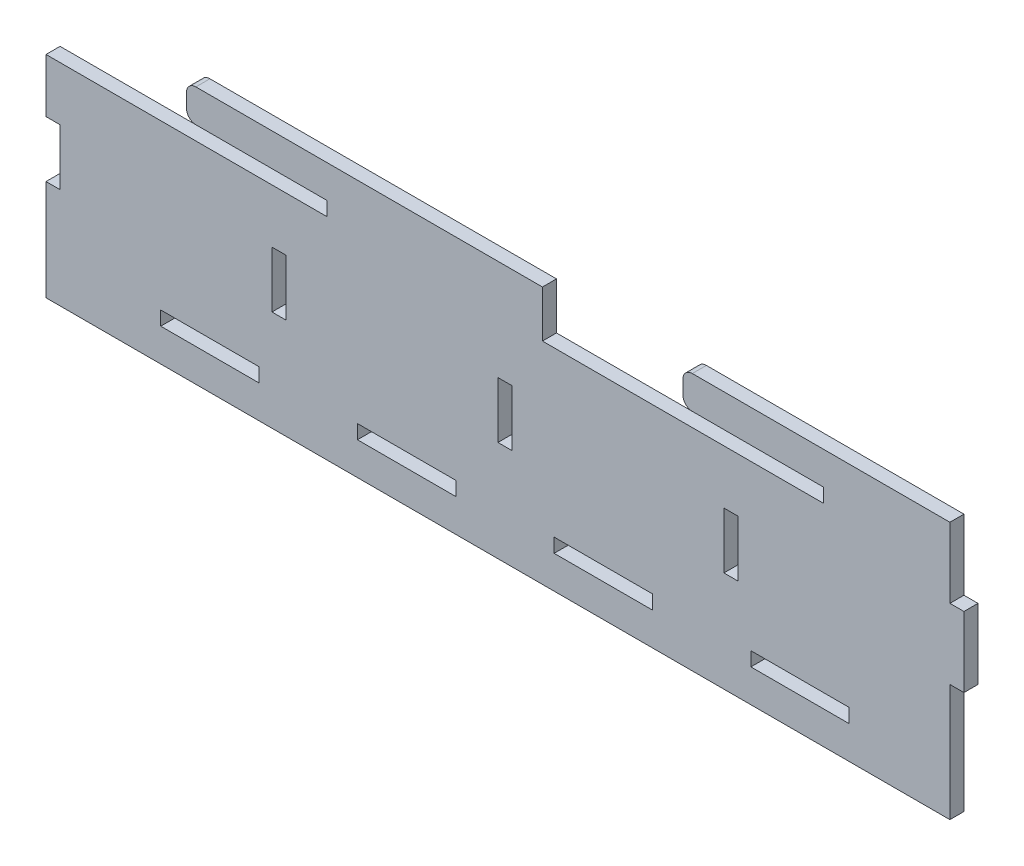
SolidWorks part; units mm, degrees
ref_plane "Front Plane" through (0, 0, 0) normal (0, 0, 1) x (1, 0, 0)
ref_plane "Top Plane" through (0, 0, 0) normal (0, 1, 0) x (1, 0, 0)
ref_plane "Right Plane" through (0, 0, 0) normal (1, 0, 0) x (0, 0, -1)
sketch "Sketch1" plane through (0, 0, 0) normal (0, 0, 1) x (1, 0, 0)
  line L0 (-102.4545, -7.25) -> (-99.4545, -7.25)
  line L1 (-102.4545, -28.75) -> (93.5455, -28.75)
  line L2 (-102.4545, -28.75) -> (-102.4545, 26.25)
  line L3 (-102.4545, 26.25) -> (93.5455, 26.25)
  line L4 (93.5455, -28.75) -> (93.5455, 26.25)
  line L5 (-102.4545, -28.75) -> (93.5455, 26.25) construction
  line L6 (-102.4545, 26.25) -> (93.5455, -28.75) construction
  line L7 (-99.4545, -7.25) -> (-99.4545, 4.75)
  line L8 (-99.4545, 4.75) -> (-102.4545, 4.75)
  line L9 (90.5455, -28.75) -> (90.5455, -3.75)
  line L10 (90.5455, -3.75) -> (93.5455, -3.75)
  line L11 (90.5455, 26.25) -> (90.5455, 11.25)
  line L12 (90.5455, 11.25) -> (93.5455, 11.25)
  line L13 (-72.4545, 26.25) -> (-72.4545, 19.25)
  line L14 (-54.2045, -7.25) -> (-51.2045, -7.25)
  line L15 (-54.2045, -7.25) -> (-54.2045, 4.75)
  line L16 (-54.2045, 4.75) -> (-51.2045, 4.75)
  line L17 (-51.2045, -7.25) -> (-51.2045, 4.75)
  line L18 (-54.2045, -7.25) -> (-51.2045, 4.75) construction
  line L19 (-54.2045, 4.75) -> (-51.2045, -7.25) construction
  line L20 (-5.9545, -7.25) -> (-2.9545, -7.25)
  line L21 (-5.9545, -7.25) -> (-5.9545, 4.75)
  line L22 (-5.9545, 4.75) -> (-2.9545, 4.75)
  line L23 (-2.9545, -7.25) -> (-2.9545, 4.75)
  line L24 (-5.9545, -7.25) -> (-2.9545, 4.75) construction
  line L25 (-5.9545, 4.75) -> (-2.9545, -7.25) construction
  line L26 (45.2955, -7.25) -> (42.2955, -7.25)
  line L27 (45.2955, -7.25) -> (45.2955, 4.75)
  line L28 (45.2955, 4.75) -> (42.2955, 4.75)
  line L29 (42.2955, -7.25) -> (42.2955, 4.75)
  line L30 (45.2955, -7.25) -> (42.2955, 4.75) construction
  line L31 (45.2955, 4.75) -> (42.2955, -7.25) construction
  line L32 (-72.4545, 19.25) -> (-42.4545, 19.25)
  line L33 (-42.4545, 19.25) -> (-42.4545, 16.25)
  line L34 (-42.4545, 16.25) -> (-102.4545, 16.25)
  line L35 (3.5455, 26.25) -> (3.5455, 16.25)
  line L36 (3.5455, 16.25) -> (63.5455, 16.25)
  line L37 (63.5455, 16.25) -> (63.5455, 19.25)
  line L38 (63.5455, 19.25) -> (33.5455, 19.25)
  line L39 (33.5455, 19.25) -> (33.5455, 26.25)
  line L41 (-77.9545, -21.75) -> (-56.9545, -21.75)
  line L42 (-77.9545, -21.75) -> (-77.9545, -18.75)
  line L43 (-77.9545, -18.75) -> (-56.9545, -18.75)
  line L44 (-56.9545, -21.75) -> (-56.9545, -18.75)
  line L45 (-77.9545, -21.75) -> (-56.9545, -18.75) construction
  line L46 (-77.9545, -18.75) -> (-56.9545, -21.75) construction
  line L47 (27.0455, -21.75) -> (6.0455, -21.75)
  line L48 (27.0455, -21.75) -> (27.0455, -18.75)
  line L49 (27.0455, -18.75) -> (6.0455, -18.75)
  line L50 (6.0455, -21.75) -> (6.0455, -18.75)
  line L51 (27.0455, -21.75) -> (6.0455, -18.75) construction
  line L52 (27.0455, -18.75) -> (6.0455, -21.75) construction
  line L53 (-14.9545, -21.75) -> (-35.9545, -21.75)
  line L54 (-14.9545, -21.75) -> (-14.9545, -18.75)
  line L55 (-14.9545, -18.75) -> (-35.9545, -18.75)
  line L56 (-35.9545, -21.75) -> (-35.9545, -18.75)
  line L57 (-14.9545, -21.75) -> (-35.9545, -18.75) construction
  line L58 (-14.9545, -18.75) -> (-35.9545, -21.75) construction
  line L71 (48.0455, -21.75) -> (69.0455, -21.75)
  line L72 (48.0455, -21.75) -> (48.0455, -18.75)
  line L73 (48.0455, -18.75) -> (69.0455, -18.75)
  line L74 (69.0455, -21.75) -> (69.0455, -18.75)
  line L75 (48.0455, -21.75) -> (69.0455, -18.75) construction
  line L76 (48.0455, -18.75) -> (69.0455, -21.75) construction
  point P0 (-67.4545, -20.25)
  point P43 (16.5455, -20.25)
  point P48 (-25.4545, -20.25)
  point P63 (58.5455, -20.25)
  dimension "D1" = 196
  dimension "D2" = 55
  dimension "D3" = 12
  dimension "D4" = 21.5
  dimension "D5" = 3
  dimension "D6" = 3
  dimension "D7" = 25
  dimension "D8" = 15
  dimension "D9" = 12
  dimension "D10" = 3
  dimension "D11" = 24.5
  dimension "D12" = 45.25
  dimension "D13" = 12
  dimension "D14" = 3
  dimension "D15" = 45.25
  dimension "D16" = 3
  dimension "D17" = 12
  dimension "D18" = 45.25
  dimension "D19" = 21
  dimension "D20" = 30
  dimension "D21" = 30
  dimension "D22" = 3
  dimension "D23" = 7
  dimension "D24" = 30
  dimension "D25" = 30
  dimension "D26" = 30
  dimension "D27" = 3
  dimension "D28" = 7
  dimension "D29" = 0
  dimension "D30" = 0
  dimension "D31" = 11.5
  dimension "D32" = 21
  dimension "D33" = 21
  dimension "D34" = 21
  dimension "D35" = 21
  dimension "D36" = 21
  dimension "D37" = 21
  dimension "D38" = 7
  dimension "D39" = 3
  dimension "D40" = 3
  dimension "D41" = 7
  dimension "D42" = 3
  dimension "D43" = 7
  dimension "D44" = 3
  dimension "D45" = 7
extrude "Boss-Extrude1" add sketch "Sketch1" along normal blind 3 contours L12 L11 L3 L2 L8 L7 L0 L1 L9 L10 L4 region at (-100.9545, -9.2857, 0)
fillet "Fillet1" radius 2 4 edges at (33.5455, 19.25, 1.5) (33.5455, 26.25, 1.5) (-72.4545, 19.25, 1.5) (-72.4545, 26.25, 1.5)
